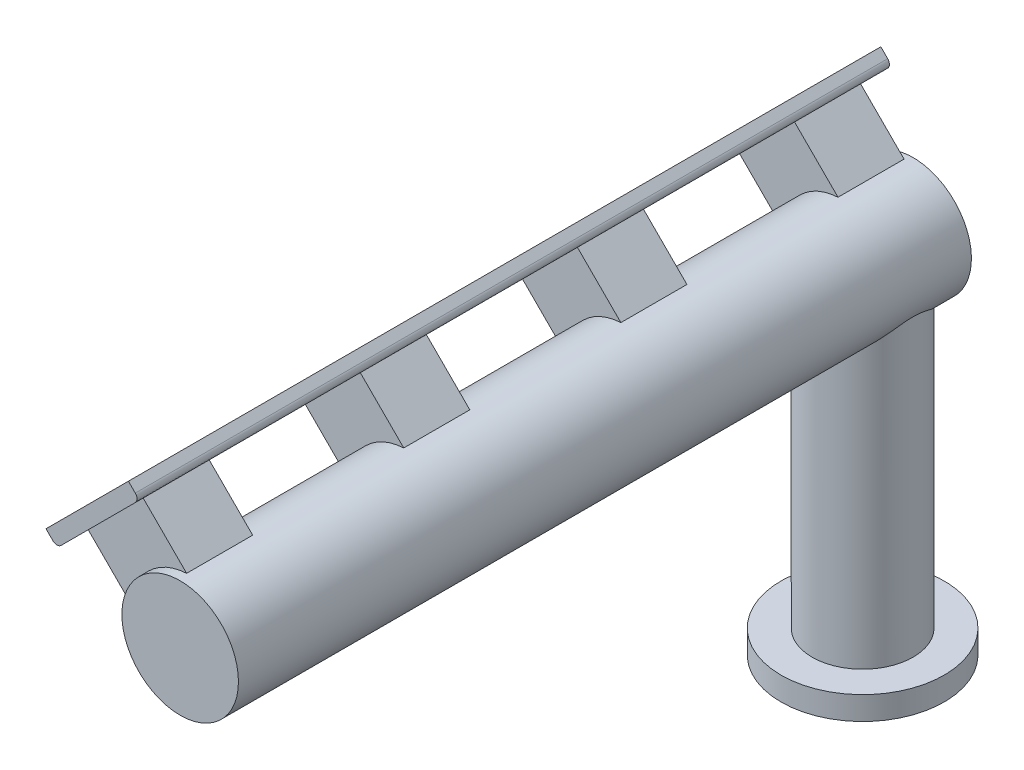
SolidWorks part; units mm, degrees
ref_plane "Front Plane" through (0, 0, 0) normal (0, 0, 1) x (1, 0, 0)
ref_plane "Top Plane" through (0, 0, 0) normal (0, 1, 0) x (1, 0, 0)
ref_plane "Right Plane" through (0, 0, 0) normal (1, 0, 0) x (0, 0, -1)
other "Configuration Table"
sketch "Sketch1" plane through (0, 0, 0) normal (0, 0, 1) x (1, 0, 0)
  line L0 (231.1886, 129.3652) -> (234.7241, 125.8297)
  line L1 (238.9667, 125.8297) -> (277.1505, 164.0134)
  line L2 (277.1505, 168.2561) -> (273.615, 171.7916)
  line L3 (273.615, 171.7916) -> (231.1886, 129.3652)
  arc A0 (234.7241, 125.8297) -> (238.9667, 125.8297) centre (236.8454, 127.951) ccw
  arc A1 (277.1505, 164.0134) -> (277.1505, 168.2561) centre (275.0292, 166.1347) ccw
extrude "Head Flange" add sketch "Sketch1" along normal blind 387.28 from offset 349.38 offset against normal yes
sketch "Sketch2" plane through (0, 0, 0) normal (0, 0, 1) x (1, 0, 0)
  line L0 (266.5439, 164.7205) -> (310.3845, 120.8799)
  line L1 (310.3845, 120.8799) -> (282.1003, 92.5956)
  line L2 (282.1003, 92.5956) -> (238.2596, 136.4363)
  line L3 (238.2596, 136.4363) -> (266.5439, 164.7205)
extrude "Primary 1" add sketch "Sketch2" along normal blind 34 from offset 5.1 offset against normal yes
sketch "Sketch3" plane through (0, 0, 0) normal (0, 0, 1) x (1, 0, 0)
  line L0 (266.5439, 164.7205) -> (310.3845, 120.8799)
  line L1 (310.3845, 120.8799) -> (282.1003, 92.5956)
  line L2 (282.1003, 92.5956) -> (238.2596, 136.4363)
  line L3 (238.2596, 136.4363) -> (266.5439, 164.7205)
extrude "Primary 3" add sketch "Sketch3" along normal blind 34 from offset 116.86 offset against normal yes
sketch "Sketch4" plane through (0, 0, 0) normal (0, 0, 1) x (1, 0, 0)
  line L0 (266.5439, 164.7205) -> (310.3845, 120.8799)
  line L1 (310.3845, 120.8799) -> (282.1003, 92.5956)
  line L2 (282.1003, 92.5956) -> (238.2596, 136.4363)
  line L3 (238.2596, 136.4363) -> (266.5439, 164.7205)
extrude "Primary 5" add sketch "Sketch4" along normal blind 34 from offset 228.62 offset against normal yes
sketch "Sketch5" plane through (0, 0, 0) normal (0, 0, 1) x (1, 0, 0)
  line L0 (266.5439, 164.7205) -> (310.3845, 120.8799)
  line L1 (310.3845, 120.8799) -> (282.1003, 92.5956)
  line L2 (282.1003, 92.5956) -> (238.2596, 136.4363)
  line L3 (238.2596, 136.4363) -> (266.5439, 164.7205)
extrude "Primary 7" add sketch "Sketch5" along normal blind 34 from offset 340.38 offset against normal yes
sketch "Sketch6" plane through (0, 0, 0) normal (0, 0, 1) x (1, 0, 0)
  circle A0 centre (296.2424, 106.7378) radius 30
extrude "Collector" add sketch "Sketch6" along normal blind 377.28 from offset 343.38 offset against normal yes
sketch "Sketch7" plane through (0, 0, 0) normal (0, 1, 0) x (1, 0, 0)
  circle A0 centre (296.2424, 317.38) radius 26
extrude "Outlet Pipe" add sketch "Sketch7" along normal blind 166.7378 from offset 60 offset against normal yes
sketch "Sketch8" plane through (0, 0, 0) normal (0, 1, 0) x (1, 0, 0)
  circle A0 centre (296.2424, 317.38) radius 42
extrude "Outlet Flange" add sketch "Sketch8" along normal blind 12 from offset 72 offset against normal yes
sketch "Sketch9" plane through (0, 0, 0) normal (0, 1, 0) x (1, 0, 0)
  circle A0 centre (296.2424, 317.38) radius 20
extrude "Outlet Bore" cut sketch "Sketch9" along normal blind 169.7378 from offset 73 offset against normal yes
